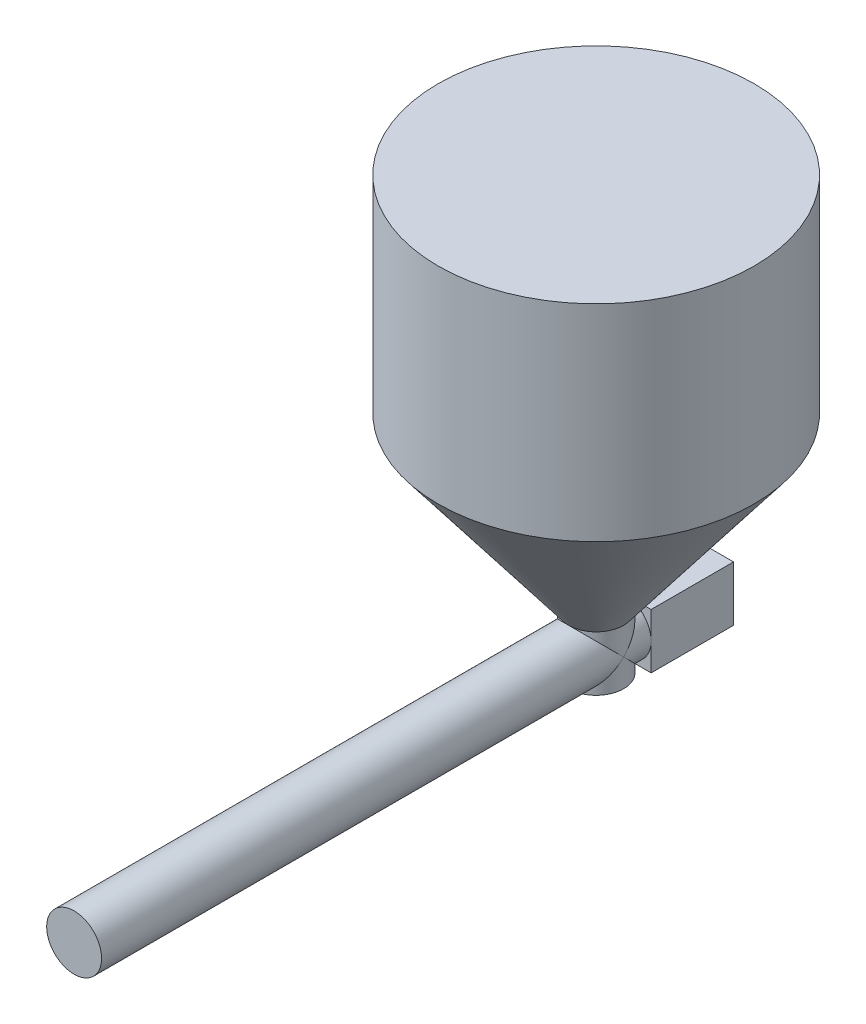
SolidWorks part; units mm, degrees
ref_plane "Alzado" through (0, 0, 0) normal (0, 0, 1) x (1, 0, 0)
ref_plane "Planta" through (0, 0, 0) normal (0, 1, 0) x (1, 0, 0)
ref_plane "Vista lateral" through (0, 0, 0) normal (1, 0, 0) x (0, 0, -1)
sketch "Croquis1" plane through (0, 0, 0) normal (0, 1, 0) x (1, 0, 0)
  circle A0 centre (0, 0) radius 115
  dimension "D1" = 230
ref_plane "Plano1" through (0, -274, 0) normal (0, 1, 0) x (1, 0, 0)
extrude "Saliente-Extruir1" add sketch "Croquis1" against normal blind 150 contours A0
sketch "Croquis2" plane through (0, -150, 0) normal (0, -1, 0) x (1, 0, 0)
  circle A1 centre (0, 0) radius 115
sketch "Croquis3" plane through (0, -274, 0) normal (0, 1, 0) x (1, 0, 0)
  circle A0 centre (0, 0) radius 20
  dimension "D1" = 40
loft "Recubrir1" add profiles "Croquis3", "Croquis2" connector at (-19.9701, -274, 1.0927) connector at (-114.7731, -150, 7.2209)
sketch "Croquis4" plane through (0, -274, 0) normal (0, -1, 0) x (1, 0, 0)
  circle A0 centre (0, 0) radius 20
  dimension "D1" = 40
extrude "Saliente-Extruir2" add sketch "Croquis4" along normal blind 40
ref_plane "Plano2" through (0, 0, -20) normal (0, 0, -1) x (-1, 0, 0)
sketch "Croquis5" plane through (0, 0, -20) normal (0, 0, -1) x (-1, 0, 0)
  line L0 (-20, -314) -> (20, -314) construction
  line L3 (0, -314) -> (0, -274) construction
  line L4 (126.5, -274) -> (-126.5, -274) construction
  circle A0 centre (0, -294) radius 20
  dimension "D1" = 40
extrude "Saliente-Extruir3" add sketch "Croquis5" against normal blind 400
sketch "Croquis6" plane through (0, 0, -20) normal (0, 0, -1) x (-1, 0, 0)
  line L0 (-20, -294) -> (20, -294) construction
  line L2 (-20, -274) -> (20, -274)
  line L3 (-20, -274) -> (-20, -314)
  line L4 (-20, -314) -> (20, -314)
  line L5 (20, -274) -> (20, -314)
  line L6 (-20, -274) -> (20, -314) construction
  line L7 (-20, -314) -> (20, -274) construction
  arc A0 (0, -274) -> (0, -314) centre (0, -294) ccw construction
  arc A1 (0, -314) -> (0, -274) centre (0, -294) ccw construction
  point P8 (0, -294)
  dimension "D1" = 40
  dimension "D2" = 40
extrude "Saliente-Extruir4" add sketch "Croquis6" along normal blind 60
